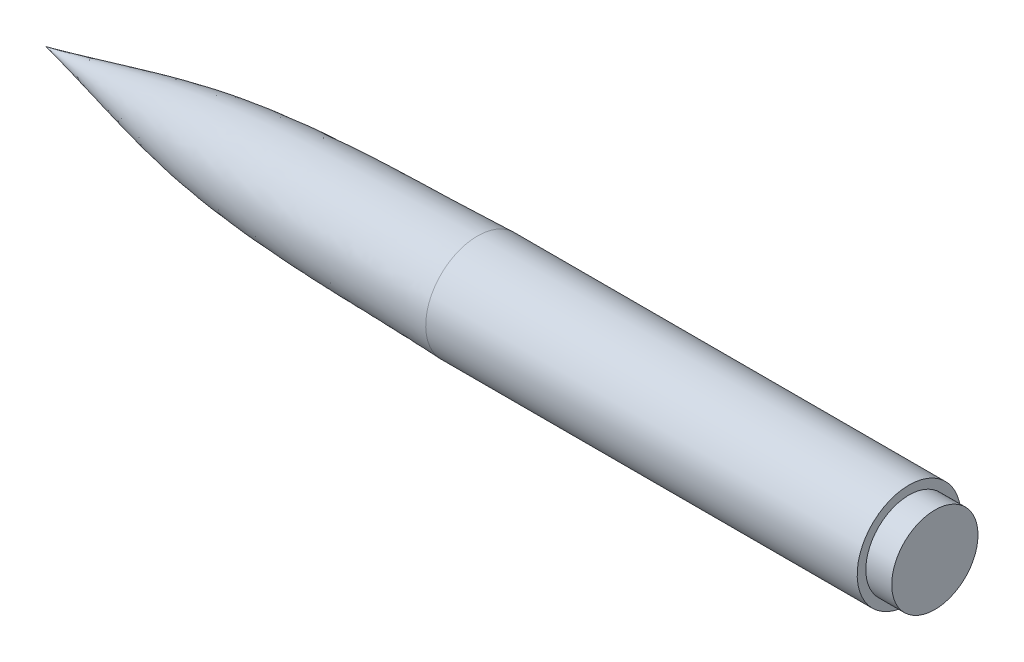
SolidWorks part; units mm, degrees
material "炭素鋼(普通)"
ref_plane "HOR" through (0, 0, 0) normal (0, 0, 1) x (1, 0, 0)
ref_plane "VERT" through (0, 0, 0) normal (0, 1, 0) x (1, 0, 0)
ref_plane "CTR" through (0, 0, 0) normal (1, 0, 0) x (0, 0, -1)
ref_axis "A_X" through (293.25, 0, 0) along (-1, 0, 0)
ref_axis "A_Y" through (0, 33, 0) along (0, -1, 0)
ref_axis "A_Z" through (0, 0, 33) along (0, 0, -1)
sketch3d "PNT_CG"
  point P0 (0, 0, 0)
sketch "Sketch1" plane through (0, 0, 0) normal (1, 0, 0) x (0, 0, -1)
  circle A0 centre (0, 0) radius 30
  dimension "D1" = 60
extrude "Boss-Extrude1" add sketch "Sketch1" along normal blind 250
sketch "Sketch2" plane through (250, 0, 0) normal (1, 0, 0) x (0, 0, -1)
  circle A0 centre (0, 0) radius 25
  dimension "D1" = 50
extrude "Boss-Extrude2" add sketch "Sketch2" along normal blind 15
sketch "Sketch3" plane through (0, 0, 0) normal (0, 0, 1) x (1, 0, 0)
  line L0 (0, 0) -> (-300, 0) construction
  line L1 (-250, 0) -> (-235.5048, 3.3465) construction
  line L2 (0, -33) -> (0, 33) construction
  line L3 (250, 30) -> (0, 30) construction
  line L4 (0, 30) -> (0, 0)
  line L5 (0, 0) -> (-250, 0)
  spline S0 degree 3 poles (-250, 0) (-221.5956, 6.1564) (-140.37, 29.8325) (-54.4987, 27.7738) (0, 30) knots 0 0 0 0 0.345337 1 1 1 1
  point P3 (-250, 0)
  dimension "D1" = 300
  dimension "D2" = 250
  dimension "D3" = 13
revolve "Revolve1" add sketch "Sketch3" angle 360 about L0
